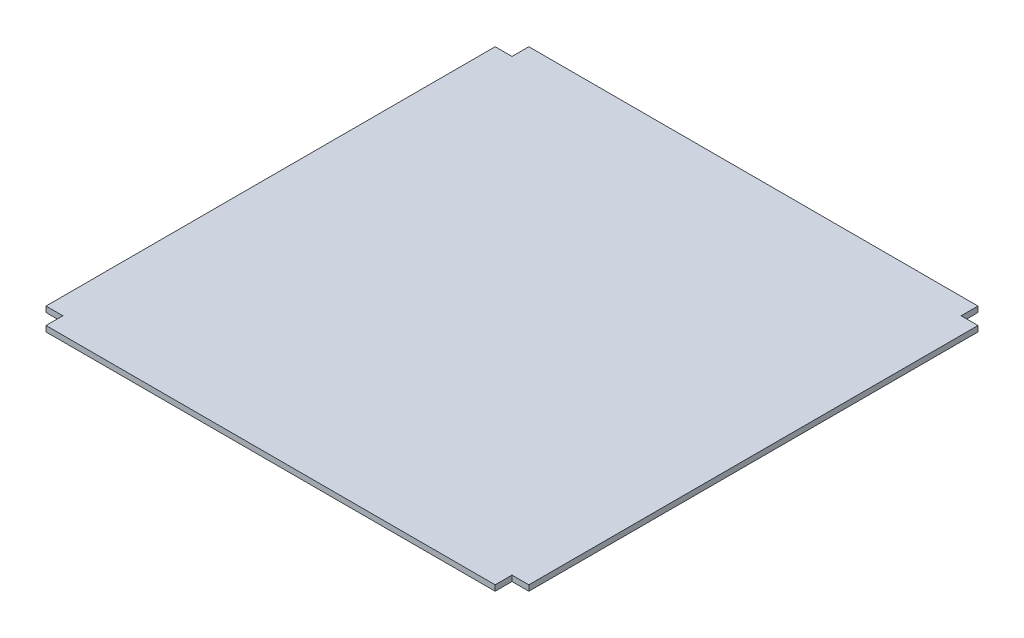
SolidWorks part; units mm, degrees
ref_plane "Front Plane" through (0, 0, 0) normal (0, 0, 1) x (1, 0, 0)
ref_plane "Top Plane" through (0, 0, 0) normal (0, 1, 0) x (1, 0, 0)
ref_plane "Right Plane" through (0, 0, 0) normal (1, 0, 0) x (0, 0, -1)
sketch "Sketch1" plane through (0, 0, 0) normal (0, 1, 0) x (1, 0, 0)
  line L0 (-430, 0) -> (430, 0) construction
  line L1 (-400, 430) -> (400, 430)
  line L2 (-430, 400) -> (-430, -400)
  line L3 (-400, -430) -> (400, -430)
  line L4 (430, 400) -> (430, -400)
  line L6 (0, 430) -> (0, -430) construction
  line L9 (-430, 400) -> (-400, 400)
  line L10 (-400, 430) -> (-400, 400)
  line L12 (-400, -430) -> (-400, -400)
  line L13 (-400, -430) -> (400, -430)
  line L14 (-430, -400) -> (-400, -400)
  line L16 (400, 430) -> (400, 400)
  line L17 (430, 400) -> (400, 400)
  line L21 (430, -400) -> (400, -400)
  line L22 (400, -430) -> (400, -400)
  line L23 (430, 400) -> (430, -400)
  point P0 (0, 0)
  point P9 (0, 0)
  dimension "D1" = 800
  dimension "D2" = 30
  dimension "D3" = 30
  dimension "D4" = 800
extrude "Boss-Extrude1" add sketch "Sketch1" along normal blind 10 contours L3 L22 L21 L4 L17 L16 L1 L10 L9 L2 L14 L12 region at (0, 0, 0)
